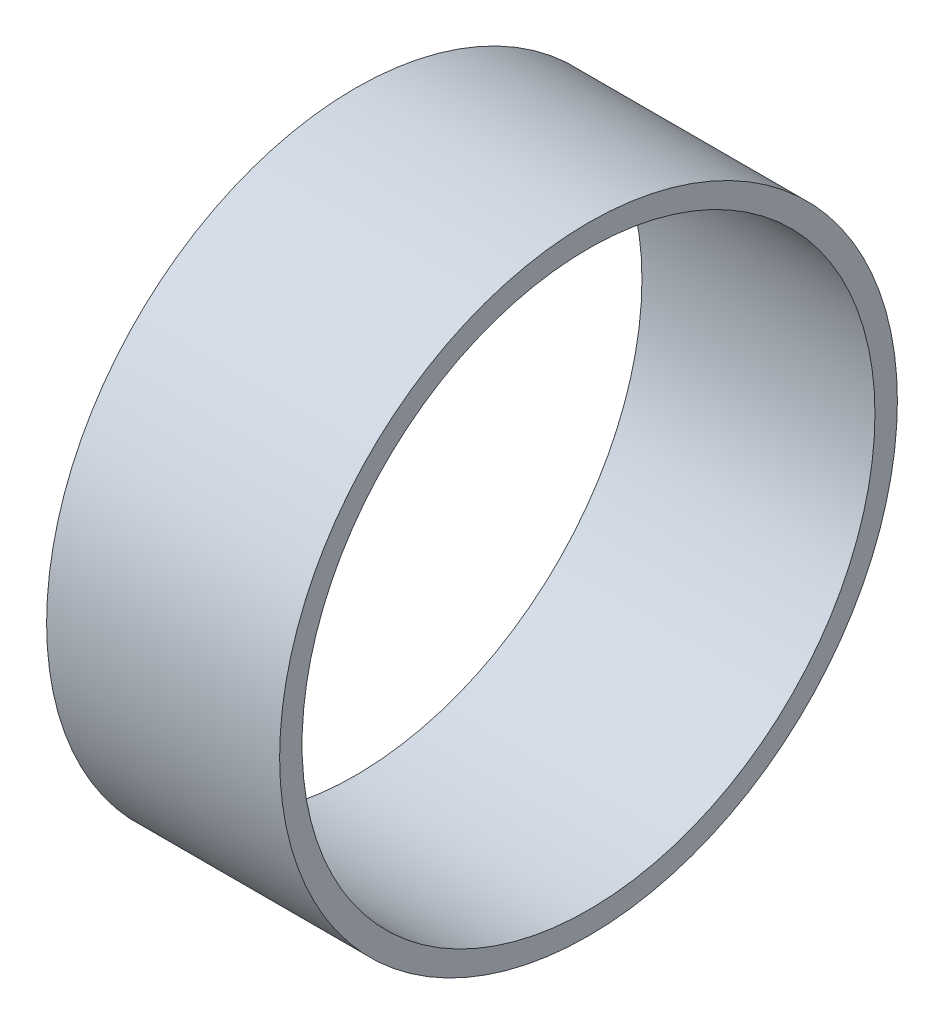
SolidWorks part; units mm, degrees
material "Copper"
ref_plane "Front Plane" through (0, 0, 0) normal (0, 0, 1) x (1, 0, 0)
ref_plane "Top Plane" through (0, 0, 0) normal (0, 1, 0) x (1, 0, 0)
ref_plane "Right Plane" through (0, 0, 0) normal (1, 0, 0) x (0, 0, -1)
sketch "Sketch1" plane through (0, 0, 0) normal (1, 0, 0) x (0, 0, -1)
  circle A0 centre (0, 0) radius 26.9367
  circle A1 centre (0, 0) radius 24.9809
  dimension "D1" = 53.8734
  dimension "D2" = 49.9618
extrude "Boss-Extrude1" add sketch "Sketch1" along normal mid plane 20.32
ref_plane "Plane1" through (0, -26.9367, 0) normal (0, -1, 0) x (-1, 0, 0)
ref_plane "Plane2" through (0, 0, -26.9367) normal (0, 0, -1) x (-1, 0, 0)
